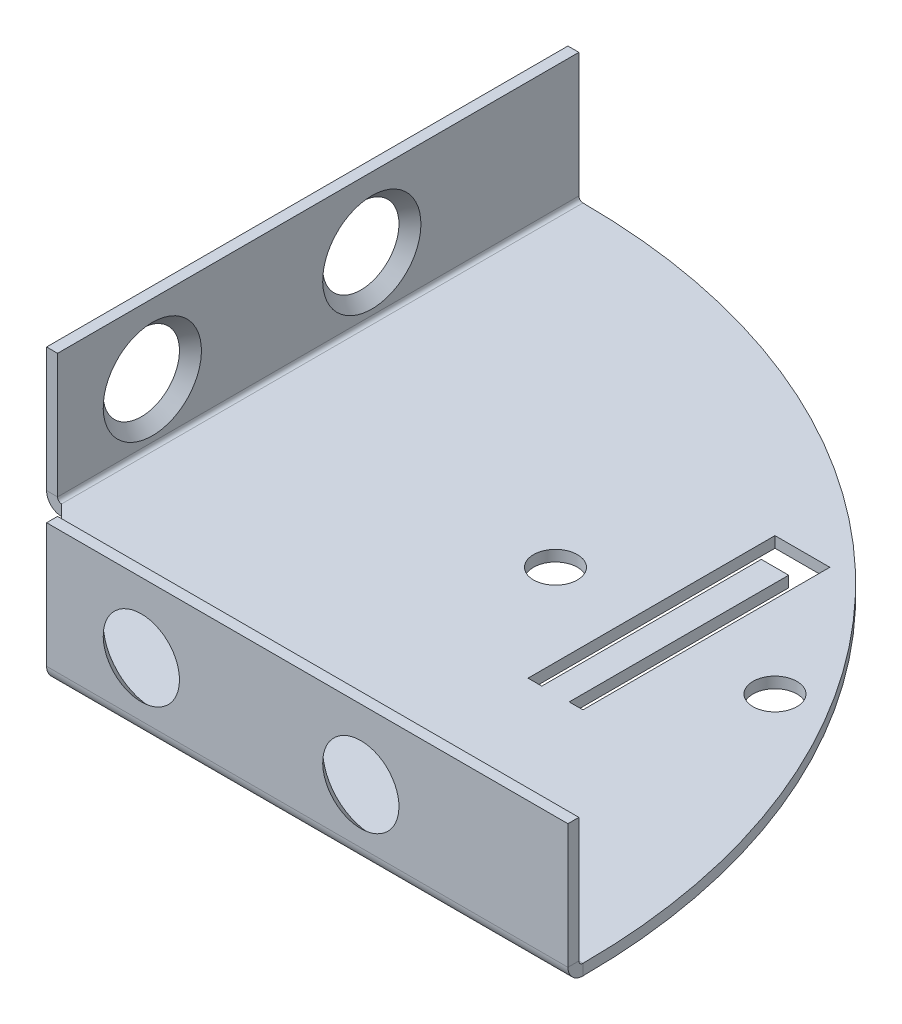
SolidWorks part; units mm, degrees
note: The reader was unsure of these and kept them because the rebuilt part matched: flange length of "Brida de arista1", "Brida de arista2".
material "7075-T6, Chapa (SS)"
ref_plane "Alzado" through (0, 0, 0) normal (0, 0, 1) x (1, 0, 0)
ref_plane "Planta" through (0, 0, 0) normal (0, 1, 0) x (1, 0, 0)
ref_plane "Vista lateral" through (0, 0, 0) normal (1, 0, 0) x (0, 0, -1)
sketch "Croquis1" plane through (0, 0, 0) normal (0, 1, 0) x (1, 0, 0)
  line L2 (0, 25) -> (25, 0)
  line L3 (0, 0) -> (25, 0) construction
  line L4 (25, 0) -> (120, 0)
  line L5 (0, 120) -> (0, 25)
  line L6 (0, 25) -> (0, 0) construction
  arc A0 (120, 0) -> (0, 120) centre (0, 0) ccw
  dimension "D1" = 120
  dimension "D2" = 25
base flange "Brida base1" sketch "Croquis1" thickness 2 reverse thickness direction no parameters "D1"=0.7366
edge flange "Brida de arista1" sketch "Croquis10" flange angle 90 flange length 25.4 flange position bend outside bend radius 0.7366 thickness 2 parameters "D6"=10
sketch "Croquis10" plane through (0, 0, 0) normal (0, 0, -1) x (-1, 0, 0)
  line L2 (-120, 0) -> (-120, 23.4)
  line L3 (-120, 23.4) -> (-25, 23.4)
  line L4 (-25, 23.4) -> (-25, 0)
  line L5 (-25, 0) -> (-120, 0) construction
  line L6 (-25, 0) -> (-120, 0)
bend "Pliegue de arista1" bend radius 0.7366 bend angle 90 parameters "D5"=1
edge flange "Brida de arista2" sketch "Croquis13" flange angle 90 flange length 25.4 flange position bend outside bend radius 0.7366 thickness 2 parameters "D6"=10
sketch "Croquis13" plane through (0, 0, 0) normal (1, 0, 0) x (0, 0, -1)
  line L2 (25, 0) -> (25, 23.4)
  line L3 (25, 23.4) -> (120, 23.4)
  line L4 (120, 23.4) -> (120, 0)
  line L5 (120, 0) -> (25, 0) construction
  line L6 (120, 0) -> (25, 0)
bend "Pliegue de arista2" bend radius 0.7366 bend angle 90 parameters "D5"=2
sketch "Croquis16" plane through (0, 0, 0) normal (0, 1, 0) x (1, 0, 0)
  line L0 (0, 0) -> (95, 0) construction
  line L2 (95, 0) -> (95, 60) construction
  line L3 (95, 60) -> (55, 60) construction
  line L5 (72.5, 40) -> (70, 40)
  line L6 (70, 85) -> (80, 85)
  line L7 (70, 85) -> (70, 35)
  line L8 (70, 35) -> (80, 35)
  line L9 (80, 85) -> (80, 35)
  line L10 (70, 85) -> (80, 35) construction
  line L11 (70, 35) -> (80, 85) construction
  line L12 (72.5, 80) -> (77.5, 80)
  line L13 (72.5, 80) -> (72.5, 40)
  line L15 (77.5, 80) -> (77.5, 40)
  line L16 (72.5, 80) -> (77.5, 40) construction
  line L17 (72.5, 40) -> (77.5, 80) construction
  line L18 (77.5, 40) -> (80, 40)
  circle A0 centre (95, 60) radius 4
  circle A1 centre (55, 60) radius 4
  point P10 (75, 60)
  point P15 (75, 60)
  dimension "D4" = 8
  dimension "D5" = 8
  dimension "D1" = 95
  dimension "D2" = 60
  dimension "D3" = 40
  dimension "D8" = 10
  dimension "D9" = 50
  dimension "D10" = 5
  dimension "D11" = 40
extrude "Cortar-Extruir3" cut sketch "Croquis16" against normal blind 10 contours A1 | A0 | L15 L18 L9 L6 L7 L5 L13 L12
sketch "Croquis17" plane through (0, 0, 0.7366) normal (0, 0, -1) x (-1, 0, 0)
  line L0 (-42.2634, 10.7) -> (-42.2634, 23.4) construction
  line L2 (-42.2634, 10.7) -> (-82.2634, 10.7) construction
  line L4 (-25, 23.4) -> (-120, 23.4) construction
  circle A0 centre (-42.2634, 10.7) radius 8.95
  circle A1 centre (-82.2634, 10.7) radius 8.95
  dimension "D2" = 17.9
  dimension "D3" = 17.9
  dimension "D1" = 12.7
  dimension "D4" = 40
extrude "Cortar-Extruir5" cut sketch "Croquis17" against normal blind 2 draft 45
sketch "Croquis18" plane through (-0.7366, 0, 0) normal (1, 0, 0) x (0, 0, -1)
  line L0 (-2.7366, 10.7) -> (42.2634, 10.7) construction
  line L2 (-2.7366, 23.4) -> (-2.7366, 0.7366) construction
  line L3 (42.2634, 10.7) -> (82.2634, 10.7) construction
  line L4 (-2.7366, 23.4) -> (-2.7366, 10.7) construction
  circle A0 centre (42.2634, 10.7) radius 8.95
  circle A1 centre (82.2634, 10.7) radius 8.95
  dimension "D4" = 17.9
  dimension "D5" = 17.9
  dimension "D1" = 45
  dimension "D2" = 40
  dimension "D3" = 12.7
extrude "Cortar-Extruir6" cut sketch "Croquis18" against normal blind 2 draft 45
sketch "Líneas de pliegue1" [suppressed] plane through (0, 0, 0) normal (0, 1, 0) x (1, 0, 0)
sketch "Cuadro delimitador1" [suppressed] plane through (0, 0, 0) normal (0, 1, 0) x (1, 0, 0)
sheet metal parameters "Chapa metálica1" thickness 2 parameters "D1"=0.7366
flat pattern "Chapa desplegada1" [suppressed]
sketch "Líneas de pliegue2" plane through (0, 0, 0) normal (0, 1, 0) x (1, 0, 0)
sketch3d "Cuadro delimitador2" [suppressed]
  line L0 (-0.0097, 0.0097, 0) -> (150, 0, 0) construction
  line L1 (0, 150, 0) -> (150.0097, 149.9903, 0) construction
  line L2 (-0.0097, 0.0097, 0) -> (0, 150, 0) construction
  line L3 (150, 0, 0) -> (150.0097, 149.9903, 0) construction
sheet metal parameters "Chapa metálica2" thickness 2 parameters "D1"=0.7366
flat pattern "Chapa desplegada1"
sketch "Líneas de pliegue2" plane through (0, 0, 0) normal (0, 1, 0) x (1, 0, 0)
  line L0 (25, 1.3727) -> (149.9875, 1.3727) construction
  line L1 (25, 1.3727) -> (149.9875, 1.3727) construction
sketch3d "Cuadro delimitador2" [suppressed]
  line L0 (0, 150, 0) -> (0, -26.2546, 0) construction
  line L1 (150, 150, 0) -> (150, -26.2546, 0) construction
  line L2 (0, 150, 0) -> (150, 150, 0) construction
  line L3 (0, -26.2546, 0) -> (150, -26.2546, 0) construction
bend of the flat pattern "Aplanar-<Pliegue de arista1>1"
sheet metal parameters "Chapa metálica3" thickness 2 parameters "D1"=0.7366
flat pattern "Chapa desplegada1"
sketch "Líneas de pliegue2" plane through (0, 0, 0) normal (0, 1, 0) x (1, 0, 0)
  line L0 (25, -1.3639) -> (150, -1.3639) construction
  line L1 (25, -1.3639) -> (150, -1.3639) construction
  line L2 (-1.3639, 150) -> (-1.3639, 25) construction
  line L3 (-1.3639, 150) -> (-1.3639, 25) construction
sketch3d "Cuadro delimitador2" [suppressed]
  line L0 (-25.3945, -25.3799, 0) -> (150, -25.3912, 0) construction
  line L1 (-25.3831, 150, 0) -> (150.0114, 149.9886, 0) construction
  line L2 (-25.3945, -25.3799, 0) -> (-25.3831, 150, 0) construction
  line L3 (150, -25.3912, 0) -> (150.0114, 149.9886, 0) construction
bend of the flat pattern "Aplanar-<Pliegue de arista1>1"
bend of the flat pattern "Aplanar-<Pliegue de arista2>1"
sheet metal parameters "Chapa metálica7" thickness 2 parameters "D1"=0.7366
flat pattern "Chapa desplegada1"
sketch "Líneas de pliegue2" plane through (0, 0, 0) normal (0, 1, 0) x (1, 0, 0)
  line L0 (25, -1.3639) -> (120, -1.3639) construction
  line L1 (25, -1.3639) -> (120, -1.3639) construction
  line L2 (-1.3639, 120) -> (-1.3639, 25) construction
  line L3 (-1.3639, 120) -> (-1.3639, 25) construction
sketch3d "Cuadro delimitador2" [suppressed]
  line L0 (120, -25.3912, 0) -> (-25.3912, -25.3912, 0) construction
  line L1 (120, 120, 0) -> (-25.3912, 120, 0) construction
  line L2 (120, -25.3912, 0) -> (120, 120, 0) construction
  line L3 (-25.3912, -25.3912, 0) -> (-25.3912, 120, 0) construction
bend of the flat pattern "Aplanar-<Pliegue de arista1>1"
bend of the flat pattern "Aplanar-<Pliegue de arista2>1"
sheet metal parameters "Chapa metálica9" thickness 2 parameters "D1"=0.7366
flat pattern "Chapa desplegada1"
sketch "Líneas de pliegue2" plane through (0, 0, 0) normal (0, 1, 0) x (1, 0, 0)
  line L0 (25, -1.3639) -> (120, -1.3639) construction
  line L1 (25, -1.3639) -> (120, -1.3639) construction
  line L2 (-1.3639, 120) -> (-1.3639, 25) construction
  line L3 (-1.3639, 120) -> (-1.3639, 25) construction
sketch3d "Cuadro delimitador2" [suppressed]
  line L0 (120, -25.3912, 0) -> (-25.3912, -25.3912, 0) construction
  line L1 (120, 120, 0) -> (-25.3912, 120, 0) construction
  line L2 (120, -25.3912, 0) -> (120, 120, 0) construction
  line L3 (-25.3912, -25.3912, 0) -> (-25.3912, 120, 0) construction
bend of the flat pattern "Aplanar-<Pliegue de arista1>1"
bend of the flat pattern "Aplanar-<Pliegue de arista2>1"
sheet metal parameters "Chapa metálica10" thickness 2 parameters "D1"=0.7366
flat pattern "Chapa desplegada1"
sketch "Líneas de pliegue2" plane through (0, 0, 0) normal (0, 1, 0) x (1, 0, 0)
  line L0 (25, -1.3639) -> (120, -1.3639) construction
  line L1 (25, -1.3639) -> (120, -1.3639) construction
  line L2 (-1.3639, 120) -> (-1.3639, 25) construction
  line L3 (-1.3639, 120) -> (-1.3639, 25) construction
sketch3d "Cuadro delimitador2" [suppressed]
  line L0 (120, -25.3912, 0) -> (-25.3912, -25.3912, 0) construction
  line L1 (120, 120, 0) -> (-25.3912, 120, 0) construction
  line L2 (120, -25.3912, 0) -> (120, 120, 0) construction
  line L3 (-25.3912, -25.3912, 0) -> (-25.3912, 120, 0) construction
bend of the flat pattern "Aplanar-<Pliegue de arista1>1"
bend of the flat pattern "Aplanar-<Pliegue de arista2>1"
